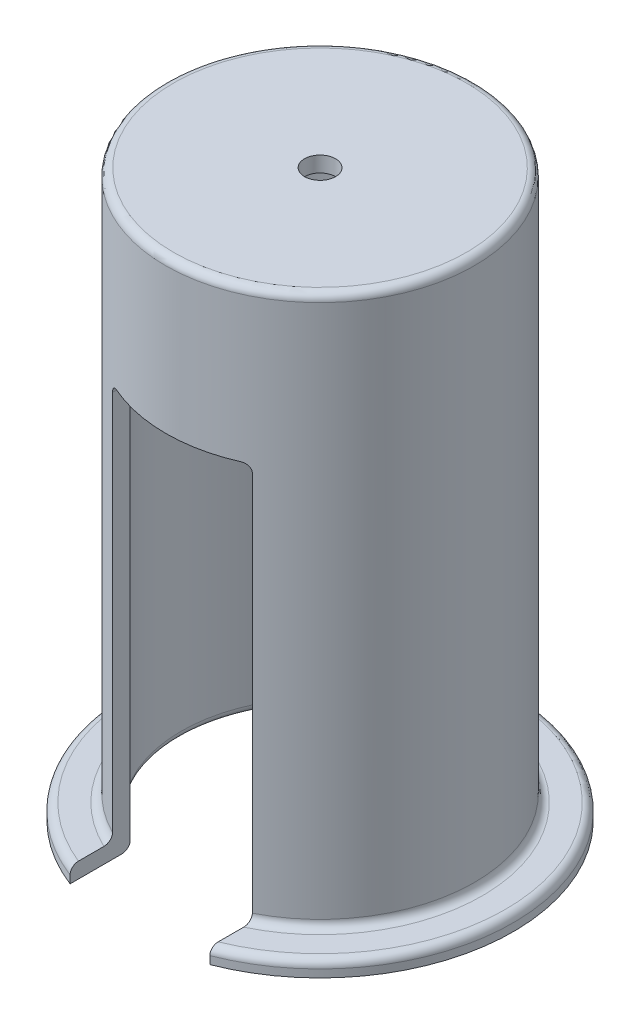
SolidWorks part; units mm, degrees
material "6061-T6 (SS)"
ref_plane "Front Plane" through (0, 0, 0) normal (0, 0, 1) x (1, 0, 0)
ref_plane "Top Plane" through (0, 0, 0) normal (0, 1, 0) x (1, 0, 0)
ref_plane "Right Plane" through (0, 0, 0) normal (1, 0, 0) x (0, 0, -1)
sketch "Sketch2" plane through (0, 0, 0) normal (0, 1, 0) x (1, 0, 0)
  circle A1 centre (0, 0) radius 9.9375
  dimension "D2" = 19.875
extrude "Boss-Extrude1" add sketch "Sketch2" along normal blind 35.384
sketch "Sketch3" plane through (0, 0, 0) normal (0, -1, 0) x (1, 0, 0)
  circle A0 centre (0, 0) radius 8.9375
  dimension "D1" = 17.875
extrude "Cut-Extrude1" cut sketch "Sketch3" against normal blind 34.384
sketch "Sketch4" plane through (0, 35.384, 0) normal (0, 1, 0) x (1, 0, 0)
  circle A0 centre (0, 0) radius 1
  dimension "D1" = 2
extrude "Cut-Extrude2" cut sketch "Sketch4" against normal through all
sketch "Sketch5" plane through (0, 0, 0) normal (0, -1, 0) x (1, 0, 0)
  circle A0 centre (0, 0) radius 12.4375
  dimension "D1" = 24.875
extrude "Boss-Extrude2" add sketch "Sketch5" along normal blind 1
sketch "Sketch6" plane through (0, -1, 0) normal (0, -1, 0) x (1, 0, 0)
  circle A0 centre (0, 0) radius 8.9375
  dimension "D1" = 17.875
extrude "Cut-Extrude3" cut sketch "Sketch6" against normal up to next
ref_plane "Plane1" through (0, 0, 15) normal (0, 0, 1) x (1, 0, 0)
sketch "Sketch7" plane through (0, 0, 15) normal (0, 0, 1) x (1, 0, 0)
  line L0 (0, -13.6813) -> (0, 13.6813) construction
  line L1 (-4.5, 25.538) -> (4.5, 25.538)
  line L2 (-4.5, 25.538) -> (-4.5, -1)
  line L3 (-4.5, -1) -> (4.5, -1)
  line L4 (4.5, 25.538) -> (4.5, -1)
  line L5 (-4.5, 25.538) -> (4.5, -1) construction
  line L6 (-4.5, -1) -> (4.5, 25.538) construction
  line L8 (-12.4375, -1) -> (12.4375, -1) construction
  point P0 (0, 12.269)
  dimension "D3" = 9
  dimension "D1" = 26.538
extrude "Cut-Extrude4" cut sketch "Sketch7" against normal up to next
fillet "Fillet1" radius 0.5 7 edges at (0, -1, -8.9375) (0, 0, -12.4375) (0, 0, -9.9375) (0, 35.384, 9.9375) (0, 34.384, -8.9375) (4.5, 25.538, 8.2911) (-4.5, 25.538, 8.2911)
equation "\"FrangiboltTotalDiameter\"= 0.625in"
equation "\"FrangiboltTotalLength\"= 0.960in"
equation "\"FrangiboltThruHoleDiameter\"= 0.169in"
equation "\"EnclosureWallThickness\"= 1mm"
equation "\"EnclosureWallSpacing\"= 1mm"
equation "\"EnclosureInnerDiameter\" = \"FrangiboltTotalDiameter\" + 2 * \"EnclosureWallSpacing\""
equation "\"EnclosureOuterDiameter\"= \"FrangiboltTotalDiameter\" + 2 * \"EnclosureWallSpacing\" + 2 * \"EnclosureWallThickness\""
equation "\"EnclosureTotalLength\"= \"FrangiboltTotalLength\" + \"DamperLength\" + \"EnclosureWallThickness\""
equation "\"D2@Sketch2\"=\"EnclosureOuterDiameter\""
equation "\"D1@Boss-Extrude1\"=\"EnclosureTotalLength\""
equation "\"DamperLength\"= 10mm"
equation "\"D1@Sketch3\"=\"EnclosureInnerDiameter\""
equation "\"D1@Cut-Extrude1\"=\"EnclosureTotalLength\"-\"EnclosureWallThickness\""
equation "\"EnclosureLip\"= 5mm"
equation "\"D1@Sketch5\"=\"EnclosureOuterDiameter\"+\"EnclosureLip\""
equation "\"D1@Boss-Extrude2\"=\"EnclosureWallSpacing\""
equation "\"D1@Sketch6\"=\"EnclosureInnerDiameter\""
equation "\"FrangiboltBoxWidth\"= 7mm"
equation "\"D3@Sketch7\"=\"FrangiboltBoxWidth\"+2mm"
equation "\"D1@Sketch7\"=\"EnclosureTotalLength\"*0.75"
